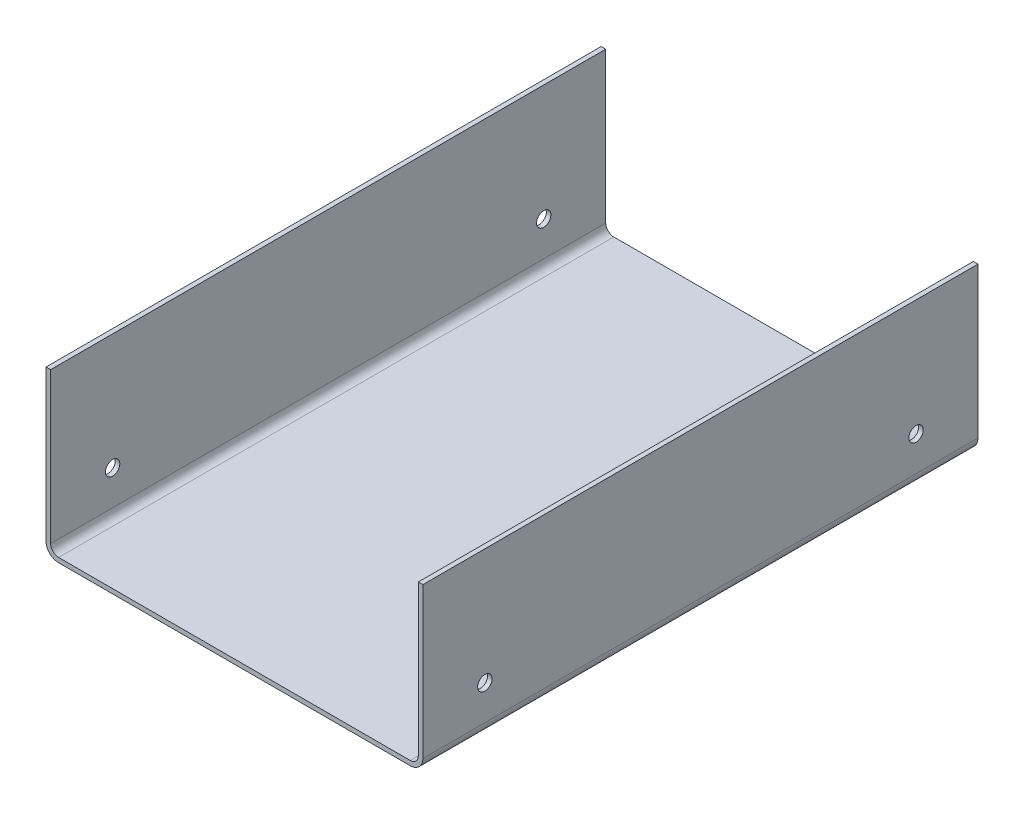
SolidWorks part; units mm, degrees
material "5052-H32"
ref_plane "Front Plane" through (0, 0, 0) normal (0, 0, 1) x (1, 0, 0)
ref_plane "Top Plane" through (0, 0, 0) normal (0, 1, 0) x (1, 0, 0)
ref_plane "Right Plane" through (0, 0, 0) normal (1, 0, 0) x (0, 0, -1)
sketch "Sketch1" plane through (0, 0, 0) normal (0, 0, 1) x (1, 0, 0)
  line L8 (127.5, 110) -> (127.5, 0)
  line L9 (-127.5, 0) -> (127.5, 0)
  line L10 (-127.5, 0) -> (-127.5, 110)
  line L11 (130.68, 110) -> (130.68, -3.18)
  line L12 (-130.68, -3.18) -> (130.68, -3.18)
  line L13 (-130.68, -3.18) -> (-130.68, 110)
  line L14 (127.5, 110) -> (130.68, 110)
  line L15 (-127.5, 110) -> (-130.68, 110)
  point P5 (0, 0)
  dimension "D2" = 110
  dimension "D4" = 110
  dimension "D3" = 255
  dimension "D1" = 3.18
extrude "Boss-Extrude1" add sketch "Sketch1" along normal blind 385
fillet "Fillet2" radius 5.5563 2 edges at (127.5, 0, 192.5) (-127.5, 0, 192.5)
fillet "Fillet3" radius 8.73 2 edges at (-130.68, -3.18, 192.5) (130.68, -3.18, 192.5)
sketch "Sketch2" plane through (130.68, 0, 0) normal (1, 0, 0) x (0, 0, -1)
  line L1 (-385, 5.55) -> (-385, 110) construction
  line L2 (0, 5.55) -> (0, 110) construction
  line L4 (-342, 29.5) -> (-342, 0) construction
  line L7 (-43, 29.5) -> (-43, 0) construction
  circle A0 centre (-342, 29.5) radius 5
  circle A1 centre (-43, 29.5) radius 5
  dimension "D3" = 10
  dimension "D4" = 10
  dimension "D1" = 43
  dimension "D2" = 29.5
  dimension "D5" = 43
  dimension "D6" = 29.5
extrude "Cut-Extrude1" cut sketch "Sketch2" against normal up to surface (261.36 mm away) up to face at (-130.68, 57.775, 192.5)
equation "\"W\"= 255"
equation "\"L\"= 385"
equation "\"Offset\"= 30"
equation "\"H\"= 110"
equation "\"Compartment Width\"= 80"
equation "\"T\"= 4.7625 * 2 / 3"
equation "\"Inside Fillet Radius\"= 5.55625"
equation "\"Hole\"=15"
equation "\"Wheel to Wall\"= 50"
equation "\"D3@Sketch1\"=\"W\""
equation "\"D2@Sketch1\"=\"H\""
equation "\"D4@Sketch1\"=\"H\""
equation "\"D1@Boss-Extrude1\"=\"L\""
equation "\"D1@Fillet2\"=\"Inside Fillet Radius\""
equation "\"D1@Fillet3\"=\"Inside Fillet Radius\"+\"T\""
